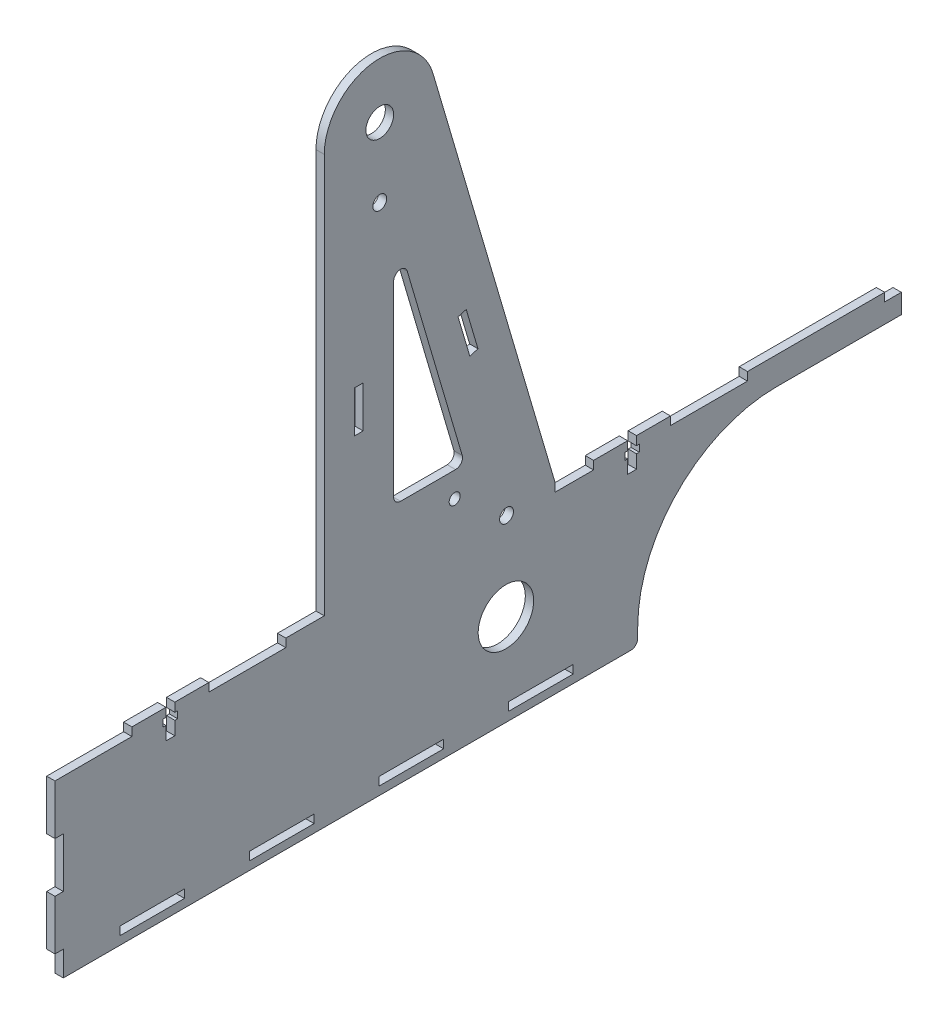
SolidWorks part; units mm, degrees
ref_plane "Front Plane" through (0, 0, 0) normal (0, 0, 1) x (1, 0, 0)
ref_plane "Top Plane" through (0, 0, 0) normal (0, 1, 0) x (1, 0, 0)
ref_plane "Right Plane" through (0, 0, 0) normal (1, 0, 0) x (0, 0, -1)
sketch "Sketch1" plane through (0, 0, 0) normal (1, 0, 0) x (0, 0, -1)
  line L0 (-152.5, 33) -> (152.5, 33)
  line L1 (152.5, 33) -> (152.5, 23)
  line L2 (-152.5, 33) -> (-152.5, -33)
  line L4 (107.5, 23) -> (152.5, 23)
  line L5 (57.5, -27) -> (57.5, -33)
  line L6 (57.5, -33) -> (-152.5, -33)
  arc A0 (57.5, -27) -> (107.5, 23) centre (107.5, -27) cw
  point P4 (-152.5, 0)
  point P7 (0, 33)
  dimension "D1" = 50
  dimension "D2" = 95
  dimension "D3" = 305
  dimension "D4" = 66
  dimension "D5" = 6
extrude "Boss-Extrude1" add sketch "Sketch1" along normal blind 3
sketch "Sketch2" plane through (3, 0, 0) normal (1, 0, 0) x (0, 0, -1)
  line L0 (-129.1567, -30) -> (-152.5, -30) construction
  line L1 (-129.1567, -30) -> (-105.8133, -30)
  line L2 (-129.1567, -30) -> (-129.1567, -27)
  line L3 (-129.1567, -27) -> (-105.8133, -27)
  line L4 (-105.8133, -30) -> (-105.8133, -27)
  line L5 (-129.1567, -30) -> (-105.8133, -27) construction
  line L6 (-129.1567, -27) -> (-105.8133, -30) construction
  line L7 (-82.47, -30) -> (-59.1266, -30)
  line L8 (-82.47, -30) -> (-82.47, -27)
  line L9 (-82.47, -27) -> (-59.1266, -27)
  line L10 (-59.1266, -30) -> (-59.1266, -27)
  line L11 (-82.47, -30) -> (-59.1266, -27) construction
  line L12 (-82.47, -27) -> (-59.1266, -30) construction
  line L13 (-35.7833, -30) -> (-12.4399, -30)
  line L14 (-35.7833, -30) -> (-35.7833, -27)
  line L15 (-35.7833, -27) -> (-12.4399, -27)
  line L16 (-12.4399, -30) -> (-12.4399, -27)
  line L17 (-35.7833, -30) -> (-12.4399, -27) construction
  line L18 (-35.7833, -27) -> (-12.4399, -30) construction
  line L19 (10.9034, -30) -> (34.2467, -30)
  line L20 (10.9034, -30) -> (10.9034, -27)
  line L21 (10.9034, -27) -> (34.2467, -27)
  line L22 (34.2467, -30) -> (34.2467, -27)
  line L23 (10.9034, -30) -> (34.2467, -27) construction
  line L24 (10.9034, -27) -> (34.2467, -30) construction
  line L25 (-152.5, 33) -> (-152.5, -33) construction
  line L26 (-105.8133, -30) -> (-82.47, -30) construction
  line L27 (-59.1266, -30) -> (-35.7833, -30) construction
  line L28 (-12.4399, -30) -> (10.9034, -30) construction
  line L29 (34.2467, -30) -> (57.5901, -30) construction
  line L30 (-152.5, -33) -> (57.5, -33) construction
  line L31 (152.5, 33) -> (-152.5, 33) construction
  line L36 (-152.5, 30) -> (-124.7727, 30)
  line L37 (-152.5, 30) -> (-152.5, 33)
  line L42 (-152.5, 33) -> (-124.7727, 33)
  line L43 (-124.7727, 30) -> (-124.7727, 33)
  line L44 (-149.5, 12) -> (-149.5, 30) construction
  line L45 (-152.5, 30) -> (-124.7727, 33) construction
  line L46 (-152.5, 33) -> (-124.7727, 30) construction
  line L47 (-149.5, -33) -> (-152.5, -33)
  line L52 (152.5, 23) -> (152.5, 33) construction
  line L53 (-97.0455, 30) -> (-69.3182, 30)
  line L54 (-97.0455, 30) -> (-97.0455, 33)
  line L55 (-97.0455, 33) -> (-69.3182, 33)
  line L56 (-69.3182, 30) -> (-69.3182, 33)
  line L57 (-97.0455, 30) -> (-69.3182, 33) construction
  line L58 (-97.0455, 33) -> (-69.3182, 30) construction
  line L59 (-41.5909, 30) -> (-13.8636, 30)
  line L60 (-41.5909, 30) -> (-41.5909, 33)
  line L61 (-41.5909, 33) -> (-13.8636, 33)
  line L62 (-13.8636, 30) -> (-13.8636, 33)
  line L63 (-41.5909, 30) -> (-13.8636, 33) construction
  line L64 (-41.5909, 33) -> (-13.8636, 30) construction
  line L65 (13.8636, 30) -> (41.5909, 30)
  line L66 (13.8636, 30) -> (13.8636, 33)
  line L67 (13.8636, 33) -> (41.5909, 33)
  line L68 (41.5909, 30) -> (41.5909, 33)
  line L69 (13.8636, 30) -> (41.5909, 33) construction
  line L70 (13.8636, 33) -> (41.5909, 30) construction
  line L71 (69.3182, 30) -> (97.0455, 30)
  line L72 (69.3182, 30) -> (69.3182, 33)
  line L73 (69.3182, 33) -> (97.0455, 33)
  line L74 (97.0455, 30) -> (97.0455, 33)
  line L75 (69.3182, 30) -> (97.0455, 33) construction
  line L76 (69.3182, 33) -> (97.0455, 30) construction
  line L77 (124.7727, 30) -> (152.5, 30)
  line L78 (124.7727, 30) -> (124.7727, 33)
  line L79 (124.7727, 33) -> (152.5, 33)
  line L80 (152.5, 30) -> (152.5, 33)
  line L81 (124.7727, 30) -> (152.5, 33) construction
  line L82 (124.7727, 33) -> (152.5, 30) construction
  line L83 (-124.7727, 30) -> (-97.0455, 30) construction
  line L84 (-69.3182, 30) -> (-41.5909, 30) construction
  line L85 (-13.8636, 30) -> (13.8636, 30) construction
  line L86 (41.5909, 30) -> (69.3182, 30) construction
  line L87 (97.0455, 30) -> (124.7727, 30) construction
  line L88 (-149.5, -33) -> (-149.5, -24)
  line L89 (-149.5, -24) -> (-152.5, -24)
  line L90 (-152.5, -33) -> (-152.5, -24)
  line L91 (-149.5, -33) -> (-152.5, -24) construction
  line L92 (-149.5, -24) -> (-152.5, -33) construction
  line L93 (-149.5, -6) -> (-152.5, -6)
  line L94 (-149.5, -6) -> (-149.5, 12)
  line L95 (-149.5, 12) -> (-152.5, 12)
  line L96 (-152.5, -6) -> (-152.5, 12)
  line L97 (-149.5, -6) -> (-152.5, 12) construction
  line L98 (-149.5, 12) -> (-152.5, -6) construction
  line L99 (-149.5, -6) -> (-149.5, -24) construction
  line L100 (146.5, 30) -> (146.5, 33)
  arc A0 (107.5, 23) -> (57.5, -27) centre (107.5, -27) ccw construction
  point P0 (-117.485, -28.5)
  point P5 (-70.7983, -28.5)
  point P10 (-24.1116, -28.5)
  point P15 (22.5751, -28.5)
  point P29 (-138.6364, 31.5)
  point P36 (-83.1818, 31.5)
  point P41 (-27.7273, 31.5)
  point P46 (27.7273, 31.5)
  point P51 (83.1818, 31.5)
  point P56 (138.6364, 31.5)
  point P61 (-151, 3)
  point P64 (-151, -28.5)
  line M15 (-152.5, 33) -> (-152.5, -33)
  line M16 (-152.5, -33) -> (57.5, -33)
  line M20 (152.5, 23) -> (152.5, 33)
  line M21 (152.5, 33) -> (-152.5, 33)
  dimension "D1" = 3
  dimension "D2" = 3
  dimension "D3" = 9
  dimension "D4" = 6
extrude "Cut-Extrude1" cut sketch "Sketch2" against normal through all both and the other way through all contours L65 L68 L66 M21 | L71 L74 L72 M21 | L36 L43 M21 M15 | L53 L56 L54 M21 | L59 L62 L60 M21 | L94 L95 L93 M15 | L88 L89 M15 M16 | L1 L4 L3 L2 | L7 L10 L9 L8 | L19 L22 L21 L20 | L100 L77 M20 M21 | L16 L15 L14 L13 region at (3, -28.5, 117.485) region at (3, -28.5, 70.7983) region at (3, -28.5, -22.5751) region at (3, 31.5, 138.6364) region at (3, 31.5, -83.1818) region at (3, 31.5, -27.7273) region at (3, 31.5, 27.7273) region at (3, 31.5, 83.1818) region at (3, -28.5, 151) region at (3, 3, 151) region at (3, 31.5, -149.5)
sketch "Sketch3" plane through (3, 0, 0) normal (1, 0, 0) x (0, 0, -1)
  line L0 (-97.0455, 33) -> (-124.7727, 33) construction
  line L1 (-112.5091, 22.5) -> (-109.3091, 22.5)
  line L2 (-112.5091, 22.5) -> (-112.5091, 33)
  line L3 (-112.5091, 33) -> (-109.3091, 33)
  line L4 (-109.3091, 22.5) -> (-109.3091, 33)
  line L5 (-112.5091, 22.5) -> (-109.3091, 33) construction
  line L6 (-112.5091, 33) -> (-109.3091, 22.5) construction
  line L7 (69.3182, 33) -> (41.5909, 33) construction
  line L8 (53.8545, 22.5) -> (57.0545, 22.5)
  line L9 (53.8545, 22.5) -> (53.8545, 33)
  line L10 (53.8545, 33) -> (57.0545, 33)
  line L11 (57.0545, 22.5) -> (57.0545, 33)
  line L12 (53.8545, 22.5) -> (57.0545, 33) construction
  line L13 (53.8545, 33) -> (57.0545, 22.5) construction
  line L14 (55.4545, 29.825) -> (55.4545, 33) construction
  line L15 (52.8545, 29.825) -> (58.0545, 29.825)
  line L16 (52.8545, 29.825) -> (52.8545, 27.325)
  line L17 (52.8545, 27.325) -> (58.0545, 27.325)
  line L18 (58.0545, 29.825) -> (58.0545, 27.325)
  line L19 (52.8545, 29.825) -> (58.0545, 27.325) construction
  line L20 (52.8545, 27.325) -> (58.0545, 29.825) construction
  line L21 (-113.5091, 29.825) -> (-108.3091, 29.825)
  line L22 (-113.5091, 29.825) -> (-113.5091, 27.325)
  line L23 (-113.5091, 27.325) -> (-108.3091, 27.325)
  line L24 (-108.3091, 29.825) -> (-108.3091, 27.325)
  line L25 (-113.5091, 29.825) -> (-108.3091, 27.325) construction
  line L26 (-113.5091, 27.325) -> (-108.3091, 29.825) construction
  line L27 (-110.9091, 29.825) -> (-110.9091, 33) construction
  point P0 (-110.9091, 27.75)
  point P7 (55.4545, 27.75)
  point P14 (55.4545, 28.575)
  point P19 (-110.9091, 28.575)
  point P24 (-110.9091, 33)
  point P25 (55.4545, 33)
  dimension "D1" = 3.2
  dimension "D2" = 10.5
  dimension "D3" = 2.5
  dimension "D4" = 5.2
  dimension "D5" = 3.175
extrude "Cut-Extrude2" cut sketch "Sketch3" against normal through all both and the other way through all contours L4 L3 L2 L1 | L23 L24 L21 L22 | L11 L10 L9 L8 | L17 L18 L15 L16
fillet "Fillet1" radius 2.5 1 edges at (1.5, -33, -57.5)
sketch "Sketch4" plane through (0, 0, 0) normal (1, 0, 0) x (0, 0, -1)
  line L0 (-55.4545, 30) -> (-55.4545, 177)
  line L2 (27.7273, 30) -> (27.7273, 33)
  line L3 (-55.4545, 30) -> (27.7273, 30)
  line L4 (-13.8636, 30) -> (-41.5909, 30) construction
  line L5 (-41.5909, 33) -> (-69.3182, 33) construction
  line L6 (27.7273, 33) -> (-16.2666, 182.6412)
  line L7 (13.8636, 33) -> (-13.8636, 33) construction
  line L8 (41.5909, 30) -> (13.8636, 30) construction
  line L9 (-149.5, -33) -> (55, -33) construction
  line L19 (-30.4545, 55) -> (-4.7987, 55)
  line L20 (-4.7987, 55) -> (-30.4545, 142.2661)
  line L21 (-30.4545, 142.2661) -> (-30.4545, 55)
  line L22 (-55.4545, 142.2661) -> (-30.4545, 142.2661) construction
  line L23 (-30.4545, 142.2661) -> (-6.4696, 149.3176) construction
  line L24 (-30.4545, 55) -> (-30.4545, 30) construction
  arc A0 (-55.4545, 177) -> (-16.2666, 182.6412) centre (-35.4545, 177) cw
  circle A1 centre (-35.4545, 177) radius 5
  point P10 (-55.4545, 33)
  point P16 (27.7273, 30)
  dimension "D2" = 10
  dimension "D3" = 15
  dimension "D1" = 210
  dimension "D4" = 25
extrude "Boss-Extrude2" add sketch "Sketch4" along normal up to surface (3 mm away) up to face at (3, -28.5, 24.1116)
fillet "Fillet2" radius 2.5 3 edges at (1.5, 55, 4.7987) (1.5, 55, 30.4545) (1.5, 142.2661, 30.4545)
ref_axis "Axis1" through (-68.2488, 177, 35.4545) along (1, 0, 0)
sketch "Sketch5" plane through (3, 0, 0) normal (1, 0, 0) x (0, 0, -1)
  line L0 (27.7273, 33) -> (27.7273, 30) construction
  line L1 (-35.4545, 152) -> (-35.4545, 177) construction
  line L2 (-3.0037, 87.8049) -> (-7.2346, 102.1958)
  line L3 (-44.4795, 83.6996) -> (-41.4295, 83.6996)
  line L4 (-44.4795, 83.6996) -> (-44.4795, 98.6996)
  line L5 (-44.4795, 98.6996) -> (-41.4295, 98.6996)
  line L6 (-41.4295, 83.6996) -> (-41.4295, 98.6996)
  line L7 (-44.4795, 83.6996) -> (-41.4295, 98.6996) construction
  line L8 (-44.4795, 98.6996) -> (-41.4295, 83.6996) construction
  line L9 (-3.0037, 87.8049) -> (-0.0775, 88.6652)
  line L10 (-7.2346, 102.1958) -> (-4.3084, 103.0561)
  line L11 (-0.0775, 88.6652) -> (-4.3084, 103.0561)
  line L12 (-3.0037, 87.8049) -> (-4.3084, 103.0561) construction
  line L13 (-7.2346, 102.1958) -> (-0.0775, 88.6652) construction
  line L14 (-55.4545, 91.1996) -> (-30.4545, 91.1996) construction
  line L15 (-55.4545, 33) -> (-55.4545, 177) construction
  line L16 (-15.6485, 91.9048) -> (8.3364, 98.9562) construction
  line L17 (-25.5561, 125.6044) -> (-5.741, 58.2051) construction
  line L18 (-16.2666, 182.6412) -> (27.7273, 33) construction
  line L19 (-30.4545, 57.5) -> (-30.4545, 124.8992) construction
  line L20 (-8.1395, 55) -> (-27.9545, 55) construction
  circle A0 centre (10.2272, 31.5) radius 2.5
  circle A1 centre (-35.4545, 152) radius 2.5
  circle A2 centre (-8.4545, 46) radius 2
  circle A3 centre (10, 0) radius 10
  point P5 (27.7273, 31.5)
  point P7 (-42.9545, 91.1996)
  point P15 (-3.656, 95.4305)
  point P30 (-42.9545, 91.1996)
  point P31 (-3.656, 95.4305)
  point P35 (-30.4545, 91.1996)
  point P36 (-15.6485, 91.9048)
  point P41 (0, 0)
  point P43 (0, 0)
  dimension "D2" = 5
  dimension "D6" = 4
  dimension "D9" = 20
  dimension "D1" = 17.5001
  dimension "D3" = 25
  dimension "D4" = 3.05
  dimension "D5" = 15
  dimension "D7" = 9
  dimension "D8" = 22
extrude "Cut-Extrude3" cut sketch "Sketch5" against normal through all both and the other way through all
